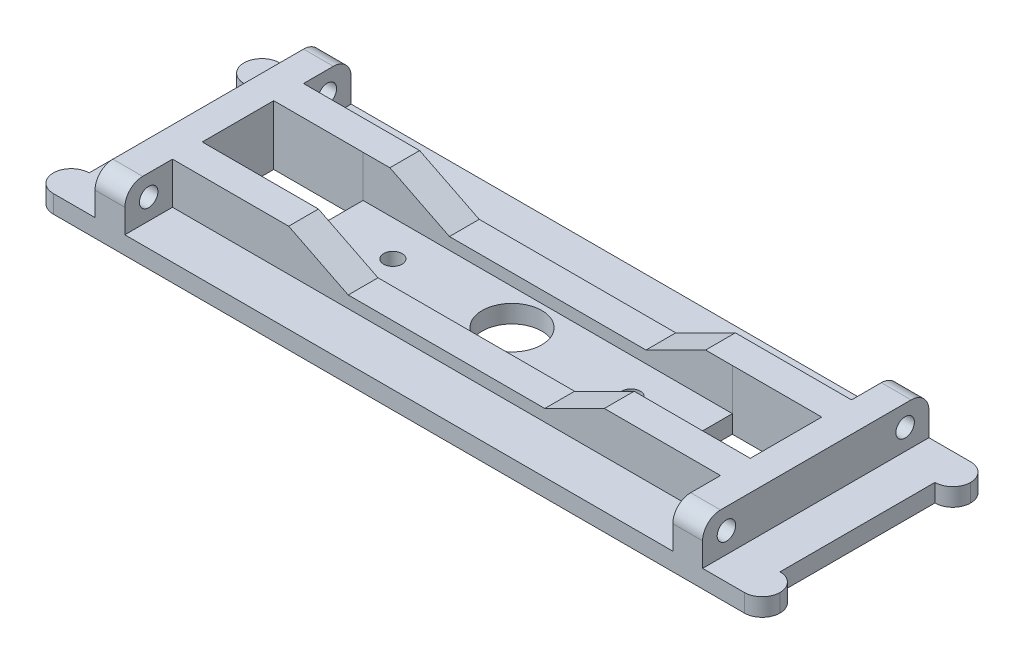
SolidWorks part; units mm, degrees
material "6061 合金"
ref_plane "前视基准面" through (0, 0, 0) normal (0, 0, 1) x (1, 0, 0)
ref_plane "上视基准面" through (0, 0, 0) normal (0, 1, 0) x (1, 0, 0)
ref_plane "右视基准面" through (0, 0, 0) normal (1, 0, 0) x (0, 0, -1)
sketch "草图1" plane through (0, 0, 0) normal (0, 1, 0) x (1, 0, 0)
  line L1 (-51, 19) -> (51, 19)
  line L2 (-51, 19) -> (-51, -19)
  line L3 (-51, -19) -> (51, -19)
  line L4 (51, 19) -> (51, -19)
  line L5 (-51, 19) -> (51, -19) construction
  line L6 (-51, -19) -> (51, 19) construction
  point P0 (0, 0)
  dimension "D1" = 102
  dimension "D2" = 38
extrude "凸台-拉伸1" add sketch "草图1" along normal mid plane 10
sketch "草图4" plane through (0, 5, 0) normal (0, 1, 0) x (1, 0, 0)
  line L0 (0, 0) -> (0, 55.7451) construction
  line L1 (61, -19) -> (51, -19)
  line L2 (61, 19) -> (51, 19)
  line L3 (51, -19) -> (51, 19)
  line L4 (61, -19) -> (61, -13)
  line L5 (61, -13) -> (58, -13)
  line L6 (51, -19) -> (51, 19) construction
  line L7 (-61, 19) -> (-61, 13)
  line L8 (-51, -19) -> (-51, 19)
  line L9 (-61, 19) -> (-51, 19)
  line L10 (0, 0) -> (85.462, 0) construction
  line L11 (-61, -19) -> (-51, -19)
  line L12 (58, -13) -> (58, 13)
  line L13 (61, 19) -> (61, 13)
  line L14 (61, 13) -> (58, 13)
  line L15 (-61, 13) -> (-58, 13)
  line L16 (-58, -13) -> (-58, 13)
  line L17 (-61, -13) -> (-58, -13)
  line L18 (-61, -19) -> (-61, -13)
  point P19 (58, 0)
  dimension "D1" = 3
  dimension "D2" = 19
  dimension "D3" = 7
  dimension "D4" = 6
extrude "凸台-拉伸2" add sketch "草图4" along normal blind 3 from vertex starting at point (-51, -5, 19)
sketch "草图23" plane through (0, 5, 0) normal (0, 1, 0) x (1, 0, 0)
  line L0 (51, -19) -> (51, 19) construction
  line L1 (46, -19) -> (-46, -19)
  line L2 (46, -19) -> (46, 19)
  line L3 (46, 19) -> (-46, 19)
  line L4 (-46, -19) -> (-46, 19)
  line L5 (46, -19) -> (-46, 19) construction
  line L6 (46, 19) -> (-46, -19) construction
  line L7 (-51, -19) -> (51, -19) construction
  point P0 (0, 0)
  dimension "D1" = 5
extrude "切除-拉伸4" cut sketch "草图23" against normal blind 7
sketch "草图25" plane through (0, -2, 0) normal (0, 1, 0) x (1, 0, 0)
  line L0 (-46, 19) -> (-46, -19) construction
  line L1 (46.5, -10.9963) -> (-46, -10.9963)
  line L2 (46.5, -10.9963) -> (46.5, -5.9963)
  line L3 (46.5, -5.9963) -> (-46, -5.9963)
  line L4 (-46, -10.9963) -> (-46, -5.9963)
  line L5 (46.5, -10.9963) -> (-46, -5.9963) construction
  line L6 (46.5, -5.9963) -> (-46, -10.9963) construction
  line L7 (10.15, 0) -> (-10.2509, 0) construction
  line L8 (-46, 10.9963) -> (-46, 5.9963)
  line L9 (46.5, 5.9963) -> (-46, 5.9963)
  line L10 (46.5, 10.9963) -> (46.5, 5.9963)
  line L11 (46.5, 10.9963) -> (-46, 10.9963)
  point P0 (0.25, -8.4963)
  dimension "D1" = 8.5
extrude "凸台-拉伸3" add sketch "草图25" along normal blind 7
sketch "草图21" plane through (0, -5, 0) normal (0, -1, 0) x (-1, 0, 0)
  line L1 (0, 0) -> (0, -48.918) construction
  line L2 (0, 0) -> (66.2962, 0) construction
  line L3 (-31, 6) -> (-31, -6)
  line L4 (-46, -6) -> (-31, -6)
  line L5 (-46, 6) -> (-46, -6)
  line L6 (-46, 6) -> (-31, 6)
  line L7 (46, 6) -> (31, 6)
  line L8 (46, 6) -> (46, -6)
  line L9 (46, -6) -> (31, -6)
  line L10 (31, 6) -> (31, -6)
  line L11 (46, 6) -> (31, -6) construction
  line L12 (46, -6) -> (31, 6) construction
  line L13 (46, 5.9963) -> (46, -5.9963) construction
  circle A0 centre (-20, 0) radius 1.55
  circle A1 centre (20, 0) radius 1.55
  circle A2 centre (0, 0) radius 5
  point P14 (38.5, 0)
  dimension "D1" = 3.1
  dimension "D5" = 10
  dimension "D2" = 15
  dimension "D3" = 20
  dimension "D4" = 12
  dimension "D6" = 7.5
extrude "切除-拉伸1" cut sketch "草图21" against normal blind 10
sketch "草图27" plane through (0, 0, 0) normal (0, 0, 1) x (1, 0, 0)
  line L1 (26.5, 12) -> (-26.5, 12)
  line L2 (26.5, 12) -> (26.5, 0)
  line L3 (26.5, 0) -> (-26.5, 0)
  line L4 (-26.5, 12) -> (-26.5, 0)
  line L5 (26.5, 12) -> (-26.5, 0) construction
  line L6 (26.5, 0) -> (-26.5, 12) construction
  point P0 (0, 6)
extrude "切除-拉伸7" cut sketch "草图27" against normal through all and the other way through all
chamfer "倒角1" distance 10 distance2 5 2 edges at (26.5, 0, -8.4963) (26.5, 0, 8.4963) first distance on face at (0, 0, -8.4963) first distance on face at (0, 0, 8.4963)
chamfer "倒角2" distance 5 distance2 10 2 edges at (-26.5, 0, -8.4963) (-26.5, 0, 8.4963) first distance on face at (-26.5, 2.5, -8.4963) first distance on face at (-26.5, 2.5, 8.4963)
sketch "Sketch2" plane through (51, 0, 0) normal (1, 0, 0) x (0, 0, -1)
  line L0 (0, 0) -> (0, 13.0611) construction
  line L1 (19, 5) -> (19, -2) construction
  line L2 (-19, 5) -> (19, 5) construction
  circle A0 centre (15, 1.5) radius 1.55
  circle A1 centre (-15, 1.5) radius 1.55
  dimension "D1" = 4
  dimension "D2" = 3.5
  dimension "D3" = 3.1
extrude "Cut-Extrude1" cut sketch "Sketch2" against normal through all
fillet "Fillet1" radius 3 8 edges at (-61, -3.5, 19) (-61, -3.5, 13) (-61, -3.5, -13) (-61, -3.5, -19) (61, -3.5, -13) (61, -3.5, -19) (61, -3.5, 19) (61, -3.5, 13)
fillet "Fillet2" radius 3 4 edges at (-48.5, 5, -19) (-48.5, 5, 19) (48.5, 5, 19) (48.5, 5, -19)
